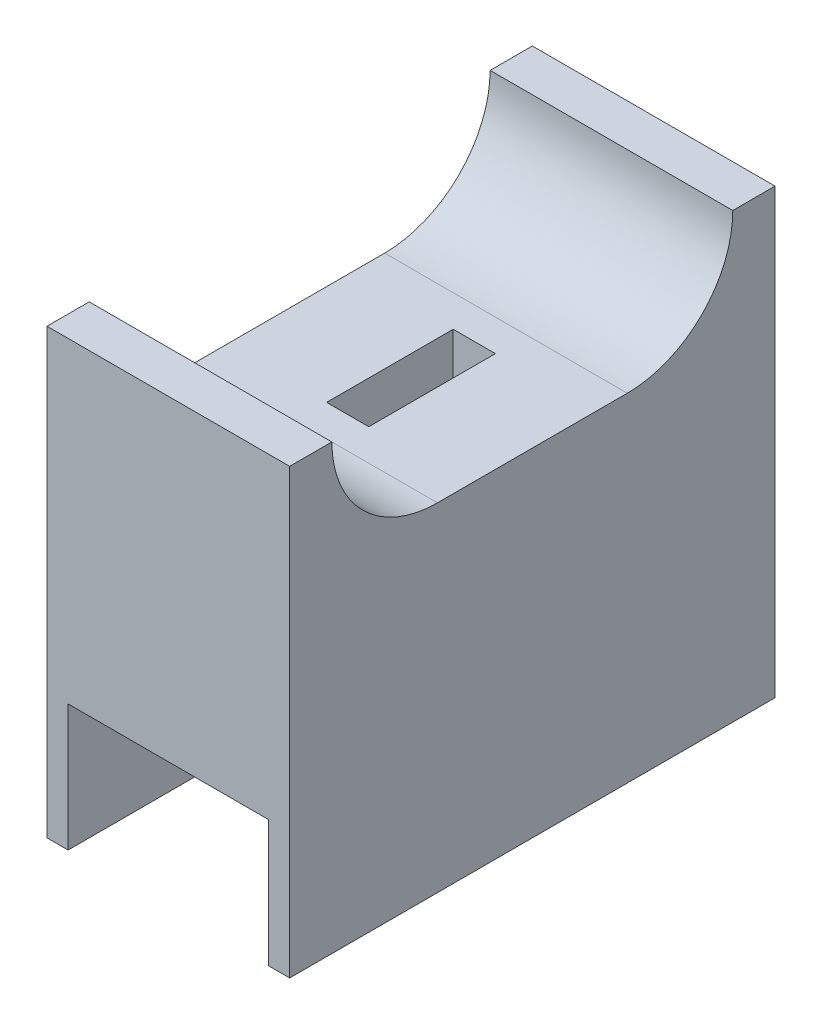
SolidWorks part; units mm, degrees
ref_plane "Front Plane" through (0, 0, 0) normal (0, 0, 1) x (1, 0, 0)
ref_plane "Top Plane" through (0, 0, 0) normal (0, 1, 0) x (1, 0, 0)
ref_plane "Right Plane" through (0, 0, 0) normal (1, 0, 0) x (0, 0, -1)
sketch "Sketch1" plane through (0, 0, 0) normal (0, 1, 0) x (1, 0, 0)
  line L1 (-5.75, -11.5) -> (5.75, -11.5)
  line L2 (-5.75, -11.5) -> (-5.75, 11.5)
  line L3 (-5.75, 11.5) -> (5.75, 11.5)
  line L4 (5.75, -11.5) -> (5.75, 11.5)
  line L5 (-5.75, -11.5) -> (5.75, 11.5) construction
  line L6 (-5.75, 11.5) -> (5.75, -11.5) construction
  point P0 (0, 0)
  dimension "D1" = 23
  dimension "D2" = 11.5
extrude "Boss-Extrude1" add sketch "Sketch1" along normal blind 11
sketch "Sketch3" plane through (0, 0, 0) normal (0, -1, 0) x (1, 0, 0)
  line L1 (-5.75, -11.5) -> (5.75, -11.5)
  line L2 (-5.75, -11.5) -> (-5.75, 11.5)
  line L3 (-5.75, 11.5) -> (5.75, 11.5)
  line L4 (5.75, -11.5) -> (5.75, 11.5)
  line L5 (-5.75, -11.5) -> (5.75, 11.5) construction
  line L6 (-5.75, 11.5) -> (5.75, -11.5) construction
  point P0 (0, 0)
extrude "Boss-Extrude3" add sketch "Sketch3" along normal blind 6
sketch "Sketch4" plane through (0, 0, 11.5) normal (0, 0, 1) x (1, 0, 0)
  line L0 (5.75, -6) -> (-5.75, -6) construction
  line L1 (-4.75, -6) -> (4.75, -6)
  line L2 (-4.75, -6) -> (-4.75, 0)
  line L3 (-4.75, 0) -> (4.75, 0)
  line L4 (4.75, -6) -> (4.75, 0)
  line L5 (-5.75, 11) -> (-5.75, -6) construction
  line L6 (5.75, 11) -> (5.75, -6) construction
  dimension "D1" = 1
  dimension "D2" = 1
  dimension "D3" = 6
extrude "Cut-Extrude1" cut sketch "Sketch4" against normal through all
sketch "Sketch7" plane through (0, 0, 0) normal (0, -1, 0) x (1, 0, 0)
  line L1 (-1, -3) -> (1, -3)
  line L2 (-1, -3) -> (-1, 3)
  line L3 (-1, 3) -> (1, 3)
  line L4 (1, -3) -> (1, 3)
  line L5 (-1, -3) -> (1, 3) construction
  line L6 (-1, 3) -> (1, -3) construction
  point P0 (0, 0)
  dimension "D1" = 2
  dimension "D2" = 6
extrude "Cut-Extrude2" cut sketch "Sketch7" against normal blind 10
sketch "Sketch8" plane through (0, 11, 0) normal (0, 1, 0) x (1, 0, 0)
  line L1 (-5.75, -11.5) -> (5.75, -11.5)
  line L2 (-5.75, -11.5) -> (-5.75, 11.5)
  line L3 (-5.75, 11.5) -> (5.75, 11.5)
  line L4 (5.75, -11.5) -> (5.75, 11.5)
  line L5 (-5.75, -11.5) -> (5.75, 11.5) construction
  line L6 (-5.75, 11.5) -> (5.75, -11.5) construction
  point P0 (0, 0)
extrude "Boss-Extrude4" add sketch "Sketch8" along normal blind 4
sketch "Sketch9" plane through (-5.75, 0, 0) normal (-1, 0, 0) x (0, 0, 1)
  line L0 (-11.5, 15) -> (11.5, 15) construction
  line L1 (-9.5, 15) -> (9.5, 15)
  line L2 (-9.5, 15) -> (-9.5, 10)
  line L3 (-9.5, 10) -> (9.5, 10)
  line L4 (9.5, 15) -> (9.5, 10)
  line L5 (-11.5, 15) -> (-11.5, -6) construction
  line L6 (11.5, 15) -> (11.5, -6) construction
  dimension "D1" = 2
  dimension "D2" = 2
  dimension "D3" = 5
extrude "Cut-Extrude3" cut sketch "Sketch9" against normal through all
fillet "Fillet1" radius 5 2 edges at (0, 10, -9.5) (0, 10, 9.5)
